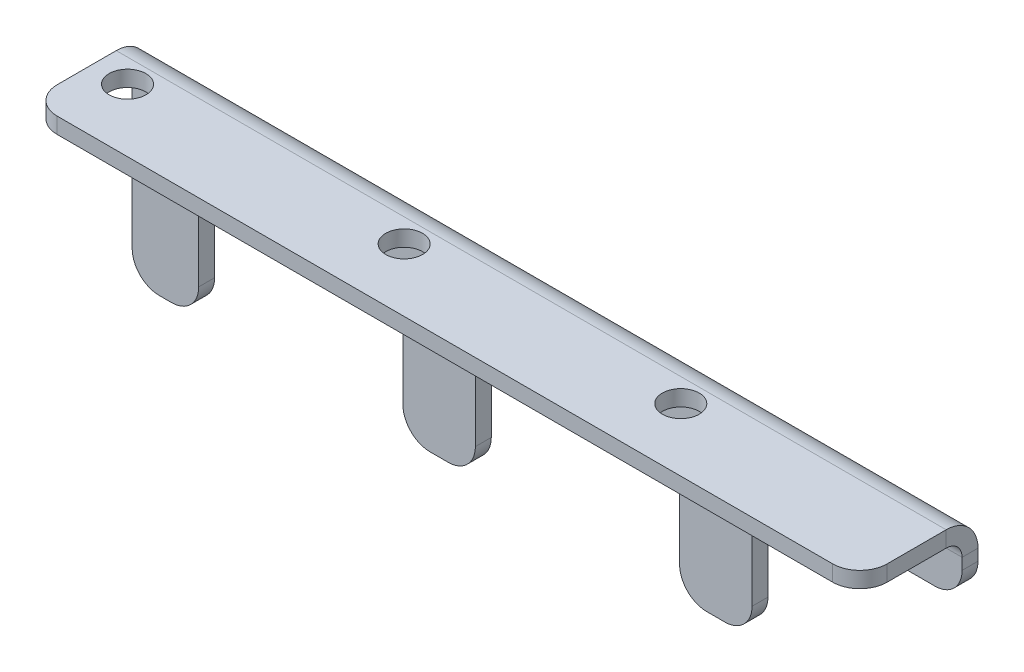
SolidWorks part; units mm, degrees
note: The reader was unsure of these and kept them because the rebuilt part matched: flange length of "Edge-Flange1".
ref_plane "Front Plane" through (0, 0, 0) normal (0, 0, 1) x (1, 0, 0)
ref_plane "Top Plane" through (0, 0, 0) normal (0, 1, 0) x (1, 0, 0)
ref_plane "Right Plane" through (0, 0, 0) normal (1, 0, 0) x (0, 0, -1)
sketch "Sketch1" plane through (0, 0, 0) normal (0, 0, -1) x (1, 0, 0)
  line L0 (17.89, 2.8316) -> (6.89, 2.8316) construction
  line L1 (0, 0) -> (60.96, 0)
  line L2 (0, 0) -> (0, 2.8316)
  line L3 (0, 2.8316) -> (60.96, 2.8316) construction
  line L4 (60.96, 0) -> (60.96, 2.8316)
  line L5 (4.89, 4.8316) -> (4.89, 104.8316) construction
  line L6 (0, 2.8316) -> (4.89, 2.8316) construction
  line L7 (0, 2.8316) -> (0, 12.8316)
  line L8 (0, 12.8316) -> (4.89, 12.8316)
  line L9 (4.89, 2.8316) -> (4.89, 12.8316)
  line L10 (19.89, 104.8316) -> (19.89, 4.8316) construction
  line L11 (19.89, 12.8316) -> (25.21, 12.8316)
  line L12 (19.89, 12.8316) -> (19.89, 2.8316)
  line L13 (19.89, 2.8316) -> (25.21, 2.8316) construction
  line L14 (25.21, 12.8316) -> (25.21, 2.8316)
  line L16 (40.21, 12.8316) -> (45.53, 12.8316)
  line L17 (40.21, 12.8316) -> (40.21, 2.8316)
  line L18 (40.21, 2.8316) -> (45.53, 2.8316) construction
  line L19 (45.53, 12.8316) -> (45.53, 2.8316)
  line L20 (45.53, 4.8316) -> (45.53, 104.8316) construction
  line L21 (25.21, 4.8316) -> (25.21, 104.8316) construction
  line L22 (4.89, 2.8316) -> (19.89, 2.8316)
  line L23 (25.21, 2.8316) -> (40.21, 2.8316)
  line L24 (45.53, 2.8316) -> (60.96, 2.8316)
  line L25 (40.21, 104.8316) -> (40.21, 4.8316) construction
  dimension "D2" = 60.96
  dimension "D1" = 10
base flange "Base-Flange1" sketch "Sketch1" thickness 1.1684 reverse thickness direction no parameters "D1"=1.1684
edge flange "Edge-Flange1" sketch "Sketch6" flange angle 90 flange length 7.5052 flange position bend outside bend radius 1.1684 thickness 1.1684 relief rectangular parameters "D6"=10
sketch "Sketch6" plane through (0, 0, 1.1684) normal (0, 1, 0) x (-1, 0, 0)
  line L0 (0, 0) -> (-60.96, 0) construction
  line L1 (0, 0) -> (-60.96, 0)
  line L2 (-60.96, 0) -> (-60.96, 7.5052)
  line L3 (-60.96, 7.5052) -> (0, 7.5052)
  line L4 (0, 7.5052) -> (0, 0)
bend "EdgeBend1" bend radius 1.1684 bend angle 90 parameters "D5"=1
sketch "Sketch7" plane through (0, 2.3368, 0) normal (0, 1, 0) x (1, 0, 0)
  line L0 (2.55, 0) -> (2.55, -4.06) construction
  line L1 (0, 0) -> (60.96, 0) construction
  line L2 (2.55, -4.06) -> (0, -4.06) construction
  line L3 (0, -2.3368) -> (0, -8.6736) construction
  line L4 (2.55, -4.06) -> (22.87, -4.06) construction
  line L5 (22.87, -4.06) -> (43.19, -4.06) construction
  dimension "D1" = 4.06
  dimension "D2" = 2.55
  dimension "D3" = 20.32
hole_wizard "Tap Drill for #6-32 Tap1" positions "Sketch8" profile "Sketch9" hole size "#6-32" standard "ANSI Inch" end condition up to next
sketch "Sketch8" plane through (0, 2.3368, 0) normal (0, 1, 0) x (1, 0, 0)
  point P0 (2.55, -4.06)
  point P3 (22.87, -4.06)
  point P6 (43.19, -4.06)
sketch "Sketch9" plane through (2.55, 2.3368, 4.06) normal (1, 0, 0) x (0, 0, 1)
  line L0 (0, 0) -> (0, 1.1684)
  line L1 (0, 1.1684) -> (1.3525, 1.1684)
  line L2 (1.3525, 1.1684) -> (1.3525, 0)
  line L5 (1.3525, 0) -> (0, 0)
  line L11 (0, -6.35) -> (0, 107.95) construction
  dimension "Thru Hole Dia." = 2.7051
  dimension "Thru Hole Depth" = 1.1684
fillet "Fillet1" radius 2 14 edges at (0, -12.8316, 0.5842) (19.89, -12.8316, 0.5842) (4.89, -12.8316, 0.5842) (25.21, -12.8316, 0.5842) (40.21, -12.8316, 0.5842) (45.53, -12.8316, 0.5842) (60.96, -2.8316, 0.5842) (60.96, 1.7526, 8.6736) (0, 1.7526, 8.6736) (45.53, -2.8316, 0.5842) (25.21, -2.8316, 0.5842) (4.89, -2.8316, 0.5842) (40.21, -2.8316, 0.5842) (19.89, -2.8316, 0.5842)
sketch "Bend-Lines1" [suppressed] plane through (0, 0, 0) normal (0, 1, 0) x (1, 0, 0)
sketch "Bounding-Box1" [suppressed] plane through (0, 0, 0) normal (0, 1, 0) x (1, 0, 0)
sheet metal parameters "Sheet-Metal8" thickness 1.1684 parameters "D1"=1.1684
flat pattern "Flat-Pattern8" [suppressed]
sketch "Bend-Lines2" plane through (0, 0, 0) normal (0, 1, 0) x (1, 0, 0)
sketch3d "Bounding-Box2" [suppressed]
  line L0 (0, -10, 0) -> (60.96, -10, 0) construction
  line L1 (0, 0, 0) -> (60.96, 0, 0) construction
  line L2 (0, -10, 0) -> (0, 0, 0) construction
  line L3 (60.96, -10, 0) -> (60.96, 0, 0) construction
sheet metal parameters "Sheet-Metal9" thickness 1.1684 parameters "D1"=1.1684
flat pattern "Flat-Pattern8"
sketch "Bend-Lines2" plane through (0, 0, 0) normal (0, 0, -1) x (-1, 0, 0)
  line L0 (0, 1.3765) -> (-60.96, 1.3765) construction
  line L1 (0, 1.3765) -> (-60.96, 1.3765) construction
sketch3d "Bounding-Box2" [suppressed]
  line L0 (0, -10, 0) -> (-60.96, -10, 0) construction
  line L1 (0, 17.0898, 0) -> (-60.96, 17.0898, 0) construction
  line L2 (0, -10, 0) -> (0, 17.0898, 0) construction
  line L3 (-60.96, -10, 0) -> (-60.96, 17.0898, 0) construction
bend of the flat pattern "Flatten-<EdgeBend1>1"
sheet metal parameters "Sheet-Metal10" thickness 1.1684 parameters "D1"=1.1684
flat pattern "Flat-Pattern8" [suppressed]
sketch "Bend-Lines2" plane through (0, 0, 0) normal (0, 0, -1) x (-1, 0, 0)
  line L0 (0, 1.3765) -> (-60.96, 1.3765) construction
  line L1 (0, 1.3765) -> (-60.96, 1.3765) construction
sketch3d "Bounding-Box2" [suppressed]
  line L0 (0, -12.8316, 0) -> (-60.96, -12.8316, 0) construction
  line L1 (0, 9.0898, 0) -> (-60.96, 9.0898, 0) construction
  line L2 (0, -12.8316, 0) -> (0, 9.0898, 0) construction
  line L3 (-60.96, -12.8316, 0) -> (-60.96, 9.0898, 0) construction
bend of the flat pattern "Flatten-<EdgeBend1>1"
sketch "Sketch7-1" plane through (0, 0.4162, 0) normal (0, 0, -1) x (1, 0, 0)
  line L0 (2.55, 0) -> (2.55, -4.06) construction
  line L2 (2.55, -4.06) -> (0, -4.06) construction
  line L4 (2.55, -4.06) -> (22.87, -4.06) construction
  line L5 (22.87, -4.06) -> (43.19, -4.06) construction
  dimension "D1" = 4.06
  dimension "D2" = 2.55
  dimension "D3" = 20.32
equation "\"slots\"= 20.32"
equation "\"D2@Sketch1\"=\"slots\"*3"
equation "\"D3@Sketch7\"=\"slots\""
